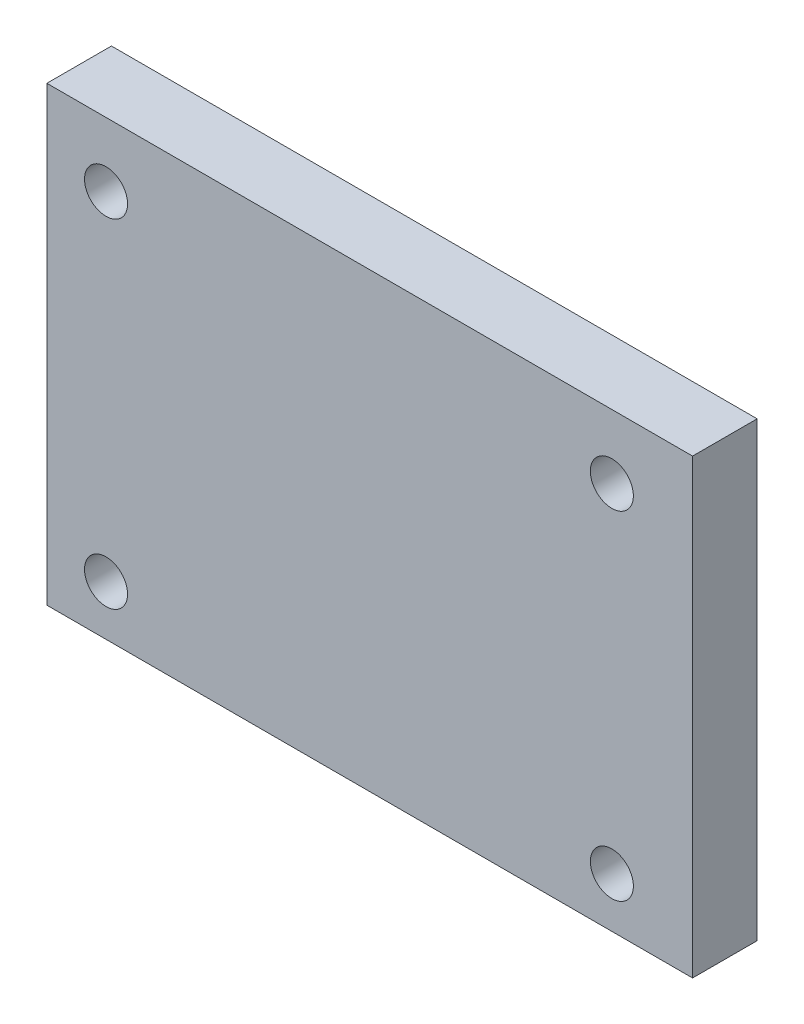
SolidWorks part; units mm, degrees
ref_plane "Plan de face" through (0, 0, 0) normal (0, 0, 1) x (1, 0, 0)
ref_plane "Plan de dessus" through (0, 0, 0) normal (0, 1, 0) x (1, 0, 0)
ref_plane "Plan de droite" through (0, 0, 0) normal (1, 0, 0) x (0, 0, -1)
sketch "Esquisse1" plane through (0, 0, 0) normal (0, 0, 1) x (1, 0, 0)
  line L1 (0, 0) -> (300, 0)
  line L2 (0, 0) -> (0, 210)
  line L3 (0, 210) -> (300, 210)
  line L4 (300, 0) -> (300, 210)
  dimension "D1" = 300
  dimension "D2" = 210
extrude "Boss.-Extru.1" add sketch "Esquisse1" along normal blind 30
sketch "Esquisse2" plane through (0, 0, 0) normal (0, 0, -1) x (-1, 0, 0)
  circle A0 centre (-27.5, 23.2059) radius 10
  circle A1 centre (-27.5, 180.2059) radius 10
  circle A2 centre (-262.5, 180.2059) radius 10
  circle A3 centre (-262.5, 23.2059) radius 10
extrude "Enlèv. mat.-Extru.1" cut sketch "Esquisse2" against normal blind 30
